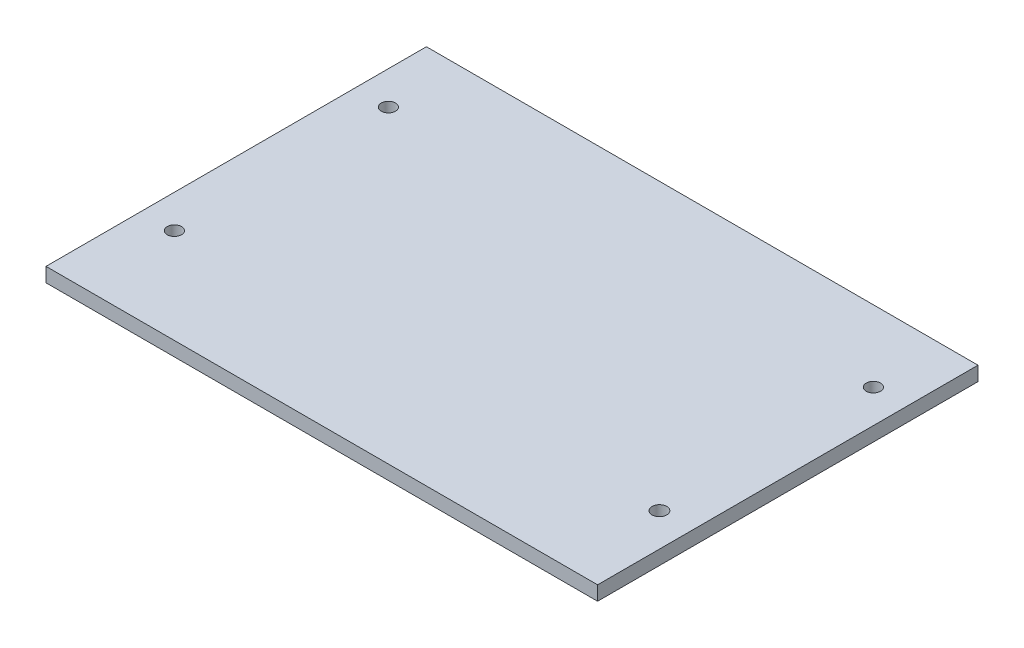
SolidWorks part; units mm, degrees
ref_plane "前视基准面" through (0, 0, 0) normal (0, 0, 1) x (1, 0, 0)
ref_plane "上视基准面" through (0, 0, 0) normal (0, 1, 0) x (1, 0, 0)
ref_plane "右视基准面" through (0, 0, 0) normal (1, 0, 0) x (0, 0, -1)
other "Configuration Table"
sketch "草图1" plane through (0, 0, 0) normal (0, 1, 0) x (1, 0, 0)
  line L1 (58, -40) -> (-58, -40)
  line L2 (58, -40) -> (58, 40)
  line L3 (58, 40) -> (-58, 40)
  line L4 (-58, -40) -> (-58, 40)
  line L5 (58, -40) -> (-58, 40) construction
  line L6 (58, 40) -> (-58, -40) construction
  point P0 (0, 0)
  dimension "D1" = 116
  dimension "D2" = 80
extrude "凸台-拉伸1" add sketch "草图1" along normal blind 3
sketch "草图2" plane through (0, 0, 0) normal (0, -1, 0) x (1, 0, 0)
  line L0 (-58, 40) -> (58, 40) construction
  line L1 (-58, -40) -> (-58, 40) construction
  line L2 (58, 40) -> (58, -40) construction
  line L3 (58, -40) -> (-58, -40) construction
  circle A0 centre (-51, 20) radius 1.5
  circle A1 centre (51, 20) radius 1.55
  circle A2 centre (51, -25) radius 1.5
  circle A3 centre (-51, -25) radius 1.5
  dimension "D1" = 20
  dimension "D2" = 7
  dimension "D3" = 7
  dimension "D4" = 20
  dimension "D5" = 15
  dimension "D6" = 7
  dimension "D7" = 7
  dimension "D8" = 15
extrude "切除-拉伸1" cut sketch "草图2" against normal blind 10
